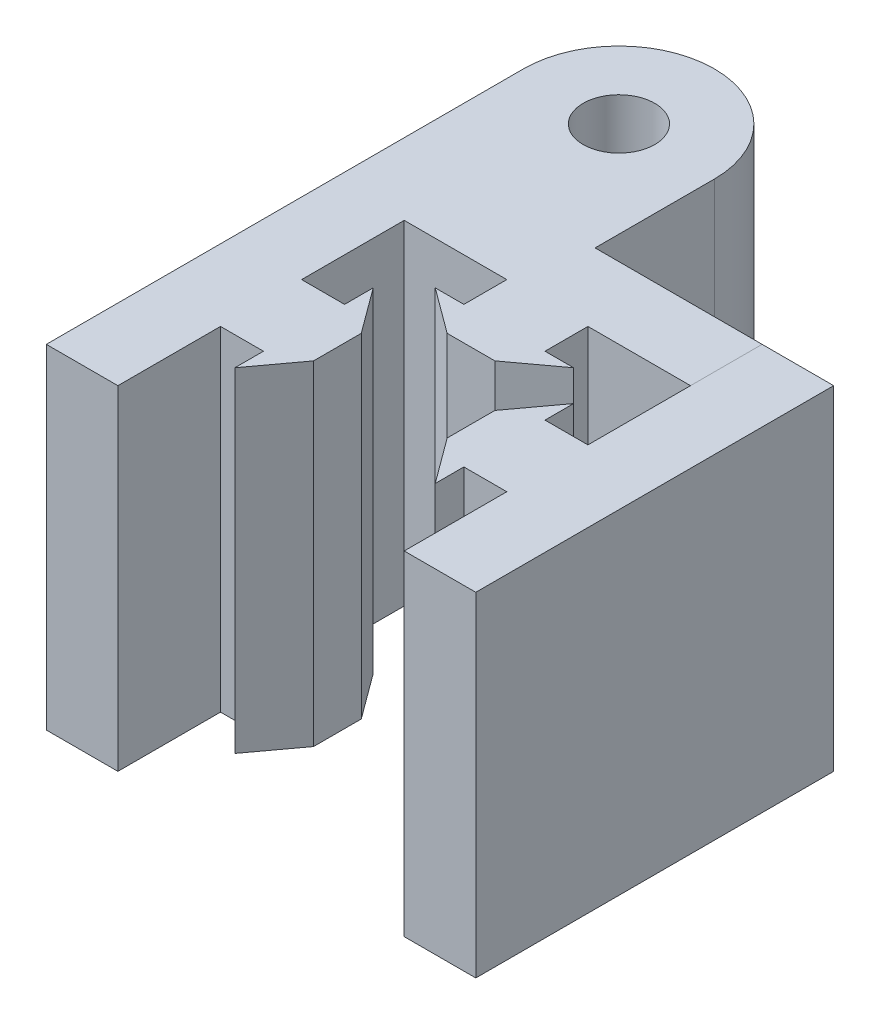
SolidWorks part; units mm, degrees
ref_plane "Plan de face" through (0, 0, 0) normal (0, 0, 1) x (1, 0, 0)
ref_plane "Plan de dessus" through (0, 0, 0) normal (0, 1, 0) x (1, 0, 0)
ref_plane "Plan de droite" through (0, 0, 0) normal (1, 0, 0) x (0, 0, -1)
ref_axis "Axe1" through (0, 17.691, 0) along (0, -1, 0)
ref_axis "Axe2" through (23.7847, 0, 0) along (-1, 0, 0)
ref_axis "Axe3" through (0, 0, -21.7718) along (0, 0, 1)
sketch "Esquisse8" plane through (0, 0, 0) normal (0, 1, 0) x (1, 0, 0)
  line L0 (-6, 1.7) -> (-4.2, 1.7)
  line L1 (0, -16.9042) -> (0, 16.9042) construction
  line L2 (-4.2, 1.7) -> (-4.2, 2.9)
  line L3 (-4.2, 2.9) -> (-2.8, 1)
  line L4 (-2.8, 1) -> (-2.8, -1)
  line L5 (-2.8, -1) -> (-4.2, -2.9)
  line L6 (-4.2, -2.9) -> (-4.2, -1.7)
  line L7 (-4.2, -1.7) -> (-6, -1.7)
  line L8 (-6, -1.7) -> (-6, -9)
  line L9 (-6, -9) -> (-9, -9)
  line L10 (-9, -9) -> (-9, 9)
  line L11 (-9, 9) -> (-6, 9)
  line L12 (-6, 9) -> (-6, 1.7)
  line L16 (23.7847, 0) -> (-17.9556, 0) construction
  point P14 (-2.8, 0)
  dimension "D1" = 1.8
  dimension "D2" = 3.2
  dimension "D3" = 18
  dimension "D4" = 2
  dimension "D5" = 1.2
  dimension "D7" = 3
  dimension "D8" = 3.4
  dimension "D9" = 6
extrude "Boss.-Extru.6" add sketch "Esquisse8" along normal mid plane 14 separate body
pattern_circular "Répétition circulaire3" count 3 every 90 about axis through (0, 17.691, 0) along (0, -1, 0) of bodies 117
sketch "Esquisse9" plane through (0, 7, 0) normal (0, 1, 0) x (1, 0, 0)
  line L0 (9, -9) -> (9, 9) construction
  line L1 (-9, -9) -> (9, -9)
  line L2 (-9, -9) -> (-9, -6)
  line L3 (-9, -6) -> (9, -6)
  line L4 (9, -9) -> (9, -6)
  dimension "D1" = 3
extrude "Enlèv. mat.-Extru.1" cut sketch "Esquisse9" against normal through all
sketch "Esquisse10" plane through (0, 0, -9) normal (0, 0, -1) x (-1, 0, 0)
  line L0 (6, -7) -> (9, -7) construction
  line L1 (9, 7) -> (1, 7)
  line L2 (9, 7) -> (9, -7)
  line L3 (9, -7) -> (1, -7)
  line L4 (1, 7) -> (1, -7)
  line L5 (-9, -7) -> (9, -7) construction
  dimension "D1" = 8
extrude "Boss.-Extru.7" add sketch "Esquisse10" along normal blind 9
fillet "Congé1" radius 4 1 edges at (-9, 0, -18)
fillet "Congé2" radius 4 1 edges at (-1, 0, -18)
sketch "Esquisse11" plane through (0, 7, 0) normal (0, 1, 0) x (1, 0, 0)
  line L0 (-9, 14) -> (-9, -6) construction
  circle A0 centre (-5, 14) radius 1.5
  dimension "D1" = 4
  dimension "D3" = 3
  dimension "D2" = 4
extrude "Enlèv. mat.-Extru.2" cut sketch "Esquisse11" against normal through all
